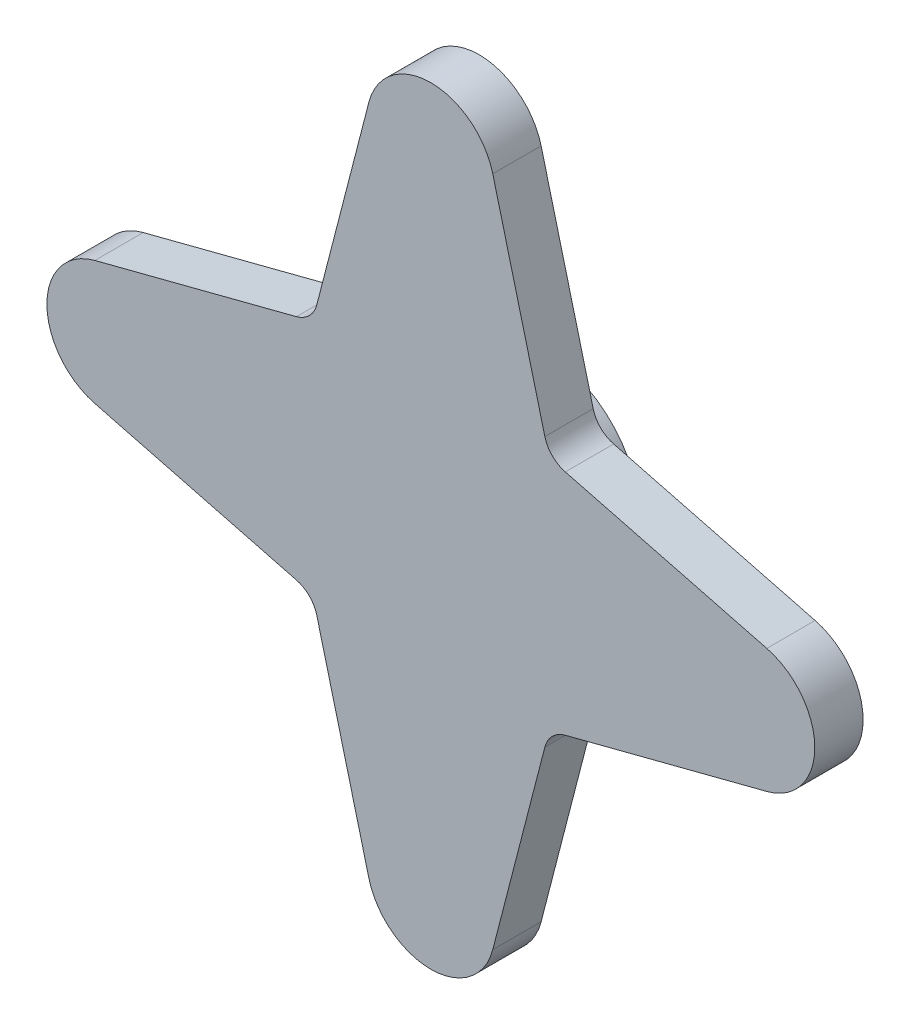
SolidWorks part; units mm, degrees
note: '?' marks a value the reader was unsure of. The reader was unsure of these and kept them because the rebuilt part matched: shared geometry of "Sketch1<9>", "Sketch1<10>".
ref_plane "Front Plane" through (0, 0, 0) normal (0, 0, 1) x (1, 0, 0)
ref_plane "Top Plane" through (0, 0, 0) normal (0, 1, 0) x (1, 0, 0)
ref_plane "Right Plane" through (0, 0, 0) normal (1, 0, 0) x (0, 0, -1)
sketch "Sketch1" plane through (0, 0, 0) normal (0, 0, 1) x (1, 0, 0)
  line L1 (-8.6, 3.45) -> (-7.5895, 2.4395)
  line L2 (-8.6, -3.45) -> (-7.5895, -2.4395)
  line L4 (-18.65, 0) -> (-5.15, 0) construction
  line L5 (-8.6, 3.45) -> (-9.3071, 4.1571)
  line L6 (-8.6, -3.45) -> (-9.3071, -4.1571)
  line L7 (-9.3071, 4.1571) -> (-16.963, 2.1784)
  line L8 (-8.6, -3.45) -> (-1.7, -3.45) construction
  line L9 (-8.6, -3.45) -> (-8.6, 3.45) construction
  line L10 (-8.6, 3.45) -> (-1.7, 3.45) construction
  line L11 (-1.7, -3.45) -> (-1.7, 3.45) construction
  line L12 (-8.6, -3.45) -> (-1.7, 3.45) construction
  line L13 (-8.6, 3.45) -> (-1.7, -3.45) construction
  line L14 (-9.3071, -4.1571) -> (-16.963, -2.1784)
  circle A0 centre (-5.15, 0) radius 3.45
  arc A1 (-16.963, 2.1784) -> (-16.963, -2.1784) centre (-16.4, 0) ccw
  circle A3 centre (-5.15, 0) radius 2.5
  dimension "D1" = 6.9
  dimension "D3" = 4.5
  dimension "D2" = 13.5
  dimension "D4" = 1
extrude "Boss-Extrude1" add sketch "Sketch1" against normal blind 2.2 contours A0 A3
ref_axis "Axis1" through (-5.15, 0, -12.1812) along (0, 0, 1)?
ref_plane "Plane3" through (-2.575, -2.575, 0) normal (0.7071, 0.7071, 0) x (0, 0, -1)
ref_plane "Plane4" through (-2.575, 2.575, 0) normal (0.7071, -0.7071, 0) x (0, 0, -1)
extrude "Boss-Extrude4" add sketch "Sketch1<9>" along normal blind 1.7 contours A0 A3 | A3
sketch "Sketch1<9>" plane through (0, 0, 0) normal (0, 0, 1) x (1, 0, 0) same geometry as "Sketch1"
extrude "Boss-Extrude5" add sketch "Sketch1<10>" along normal blind 1.7
sketch "Sketch1<10>" plane through (0, 0, 0) normal (0, 0, 1) x (1, 0, 0) same geometry as "Sketch1"
mirror "Mirror2" about plane through (-2.575, 2.575, 0) normal (0.7071, -0.7071, 0) of "Boss-Extrude5"
mirror "Mirror3" about plane through (-2.575, -2.575, 0) normal (0.7071, 0.7071, 0) of "Mirror2", "Boss-Extrude5"
fillet "Fillet1" radius 1 4 edges at (-9.3071, -4.1571, 0.85) (-0.9929, -4.1571, 0.85) (-0.9929, 4.1571, 0.85) (-9.3071, 4.1571, 0.85)
sketch "Sketch2" plane through (0, 0, 0) normal (0, 0, -1) x (-1, 0, 0)
  circle A1 centre (5.15, 0) radius 2.5
  circle A2 centre (5.15, 0) radius 2.5
  dimension "D1" = 0
extrude "0ZvarianceBoss" add sketch "Sketch2" along normal blind 0.2
